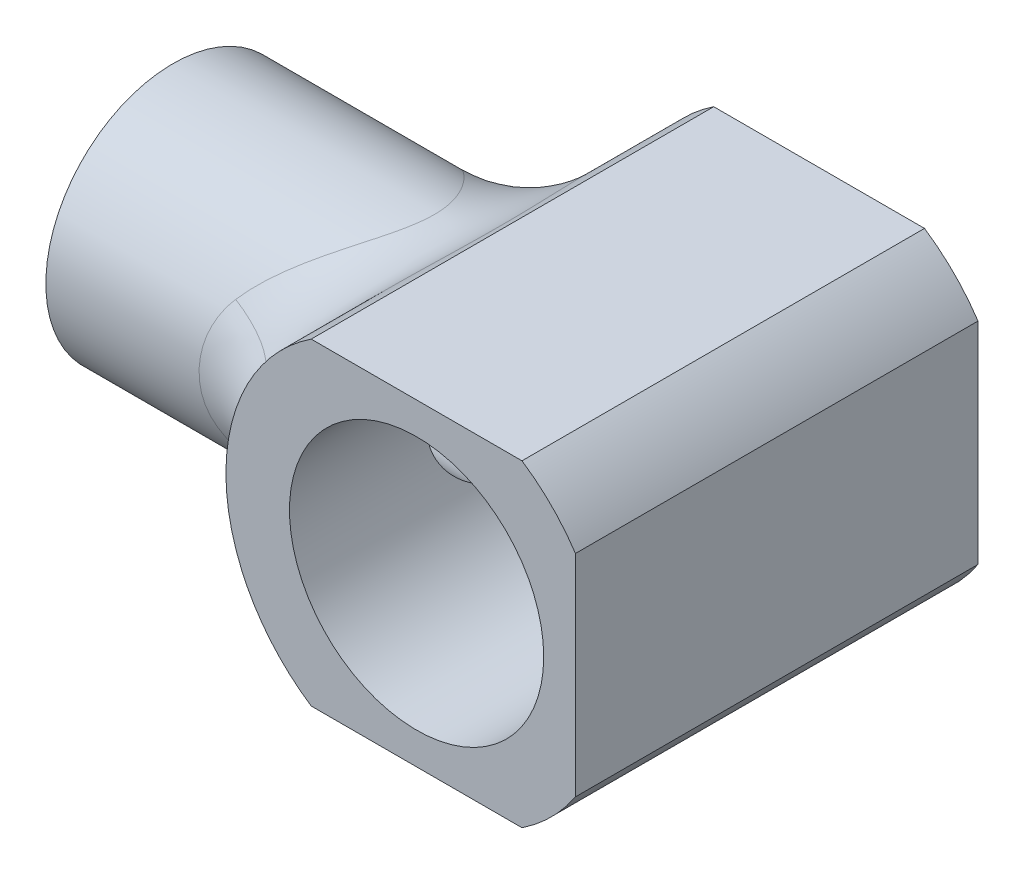
SolidWorks part; units mm, degrees
ref_plane "Front Plane" through (0, 0, 0) normal (0, 0, 1) x (1, 0, 0)
ref_plane "Top Plane" through (0, 0, 0) normal (0, 1, 0) x (1, 0, 0)
ref_plane "Right Plane" through (0, 0, 0) normal (1, 0, 0) x (0, 0, -1)
sketch "Sketch1" plane through (0, 0, 0) normal (0, 0, 1) x (1, 0, 0)
  circle A0 centre (0, 0) radius 6
  circle A1 centre (0, 0) radius 9
  dimension "D1" = 12
  dimension "D2" = 18
extrude "LM6UU_Support" add sketch "Sketch1" along normal mid plane 19
sketch "Sketch2" plane through (0, 0, 0) normal (1, 0, 0) x (0, 0, -1)
  circle A0 centre (0, 0) radius 3
  circle A1 centre (0, 0) radius 6
  dimension "D1" = 6
  dimension "D2" = 12
extrude "ShaftSupport" add sketch "Sketch2" against normal blind 21
sketch "Sketch3" plane through (0, 0, -9.5) normal (0, 0, -1) x (-1, 0, 0)
  circle A0 centre (0, 0) radius 6
  dimension "D1" = 12
extrude "LM6UU_CentralHole" cut sketch "Sketch3" against normal through all
fillet "Fillet1" radius 5 1 edges at (-8.9625, 0.8209, -5.9436)
sketch "Sketch4" plane through (-21, 0, 0) normal (-1, 0, 0) x (0, 0, 1)
  circle A0 centre (0, 0) radius 3
  dimension "D1" = 6
extrude "Cut-Extrude2" cut sketch "Sketch4" against normal up to surface (15 mm away) up to face at (6, 0, 9.5)
sketch "Sketch5" plane through (0, 0, 9.5) normal (0, 0, 1) x (1, 0, 0)
  line L0 (0, -9.9) -> (0, 9.9) construction
  line L1 (-4.9749, 9) -> (4.9749, 9)
  line L2 (-4.9749, 9) -> (-4.9749, 7.5)
  line L3 (-4.9749, 7.5) -> (4.9749, 7.5)
  line L4 (4.9749, 9) -> (4.9749, 7.5)
  line L5 (-4.9749, -7.5) -> (4.9749, -7.5)
  line L6 (-4.9749, -7.5) -> (-4.9749, -9)
  line L7 (-4.9749, -9) -> (4.9749, -9)
  line L8 (4.9749, -7.5) -> (4.9749, -9)
  line L9 (7.5, 4.9749) -> (9, 4.9749)
  line L10 (7.5, 4.9749) -> (7.5, -4.9749)
  line L11 (7.5, -4.9749) -> (9, -4.9749)
  line L12 (9, 4.9749) -> (9, -4.9749)
  circle A0 centre (0, 0) radius 9 construction
  arc A1 (-8.2639, -3.5648) -> (-8.2639, 3.5648) centre (0, 0) ccw construction
  point P17 (6.722, -5.9845)
  point P18 (6.8132, 5.8805)
  point P19 (6.8433, 5.8454)
  dimension "D1" = 15
  dimension "D2" = 7.5
extrude "Cut-Extrude3" cut sketch "Sketch5" against normal through all
